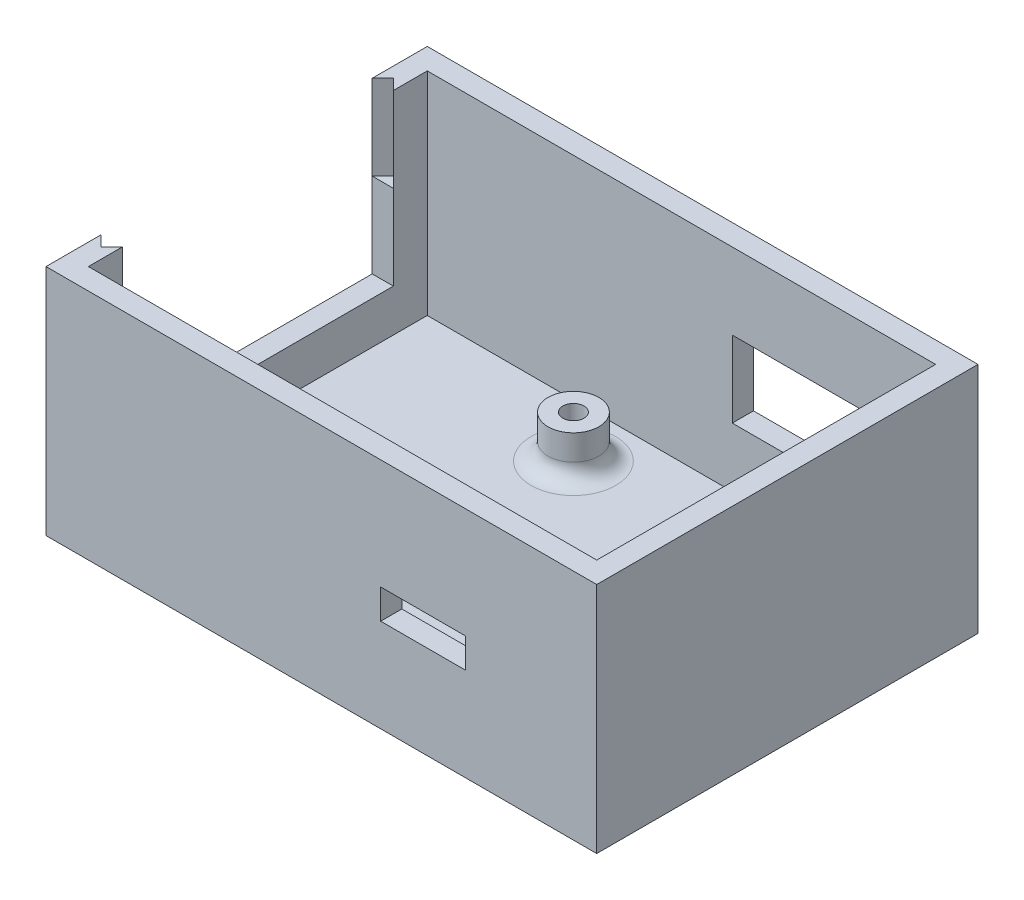
SolidWorks part; units mm, degrees
ref_plane "前视基准面" through (0, 0, 0) normal (0, 0, 1) x (1, 0, 0)
ref_plane "上视基准面" through (0, 0, 0) normal (0, 1, 0) x (1, 0, 0)
ref_plane "右视基准面" through (0, 0, 0) normal (1, 0, 0) x (0, 0, -1)
sketch "草图1" plane through (0, 0, 0) normal (0, 1, 0) x (1, 0, 0)
  line L1 (-32.5, 22.5) -> (32.5, 22.5)
  line L2 (-32.5, 22.5) -> (-32.5, -22.5)
  line L3 (-32.5, -22.5) -> (32.5, -22.5)
  line L4 (32.5, 22.5) -> (32.5, -22.5)
  line L5 (-32.5, 22.5) -> (32.5, -22.5) construction
  line L6 (-32.5, -22.5) -> (32.5, 22.5) construction
  point P0 (0, 0)
  dimension "D1" = 65
  dimension "D2" = 45
extrude "凸台-拉伸1" add sketch "草图1" along normal blind 27.5
shell "抽壳1" thickness 2.5 removed face at (0, 27.5, 0)
sketch "草图3" plane through (-30, 0, 0) normal (1, 0, 0) x (0, 0, -1)
  line L0 (20, 27.5) -> (-20, 27.5) construction
  line L1 (16, 27.5) -> (-16, 27.5)
  line L2 (16, 27.5) -> (16, 7.5)
  line L3 (16, 7.5) -> (-16, 7.5)
  line L4 (-16, 27.5) -> (-16, 7.5)
  line L5 (0, 27.5) -> (0, 7.5) construction
  line L6 (20, 2.5) -> (-20, 2.5) construction
  point P10 (0, 2.5)
  dimension "D1" = 32
  dimension "D2" = 5
extrude "切除-拉伸1" cut sketch "草图3" against normal through all
sketch "草图4" plane through (0, 27.5, 0) normal (0, 1, 0) x (1, 0, 0)
  line L0 (-32.5, 16) -> (-31.25, 17.25)
  line L1 (-31.25, 17.25) -> (-30, 16)
  line L2 (-32.5, 16) -> (-30, 16)
  line L3 (-32.5, -16) -> (-30, -16)
  line L4 (-30, 20) -> (-30, -20) construction
  line L5 (-32.5, -16) -> (-30, -16) construction
  line L6 (-30, -16) -> (-31.25, -17.25)
  line L7 (-31.25, -17.25) -> (-32.5, -16)
extrude "切除-拉伸2" cut sketch "草图4" against normal offset from surface (10 mm away) 10 up to face at (-31.25, 7.5, 0)
sketch "草图5" plane through (0, 2.5, 0) normal (0, 1, 0) x (1, 0, 0)
  line L0 (0, 0) -> (-37.9244, 0) construction
  line L1 (-32.5, -16) -> (-32.5, 16) construction
  circle A0 centre (-6.5, 13.75) radius 3
  circle A1 centre (-6.5, -13.75) radius 3
  circle A2 centre (-6.5, 13.75) radius 1.25
  circle A3 centre (-6.5, -13.75) radius 1.25
  dimension "D1" = 6
  dimension "D2" = 13.75
  dimension "D5" = 2.5
  dimension "D3" = 27.5
  dimension "D4" = 26
extrude "凸台-拉伸2" add sketch "草图5" along normal blind 5
sketch "草图6" plane through (0, 2.5, 0) normal (0, 1, 0) x (1, 0, 0)
  line L0 (30, -20) -> (30, 20) construction
  line L1 (30, 20) -> (-30, 20) construction
  circle A0 centre (20, -7) radius 3
  circle A1 centre (20, -7) radius 0.75
  dimension "D2" = 6
  dimension "D3" = 1.5
  dimension "D1" = 10
  dimension "D4" = 27
extrude "凸台-拉伸3" add sketch "草图6" along normal blind 5
sketch "草图7" plane through (0, 0, -20) normal (0, 0, 1) x (1, 0, 0)
  line L0 (30, 27.5) -> (30, 2.5) construction
  line L1 (28, 18.5) -> (6, 18.5)
  line L2 (28, 18.5) -> (28, 9.5)
  line L3 (28, 9.5) -> (6, 9.5)
  line L4 (6, 18.5) -> (6, 9.5)
  line L5 (30, 2.5) -> (-30, 2.5) construction
  dimension "D1" = 2
  dimension "D2" = 9
  dimension "D3" = 22
  dimension "D4" = 7
extrude "切除-拉伸3" cut sketch "草图7" against normal through all
sketch "草图8" plane through (0, 0, 20) normal (0, 0, -1) x (-1, 0, 0)
  line L0 (-30, 27.5) -> (-30, 2.5) construction
  line L1 (-7, 14.5) -> (-17, 14.5)
  line L2 (-7, 14.5) -> (-7, 11)
  line L3 (-7, 11) -> (-17, 11)
  line L4 (-17, 14.5) -> (-17, 11)
  line L5 (30, 2.5) -> (-30, 2.5) construction
  dimension "D1" = 13
  dimension "D2" = 10
  dimension "D3" = 3.5
  dimension "D4" = 8.5
extrude "切除-拉伸4" cut sketch "草图8" against normal through all
fillet "圆角1" radius 2 3 edges at (20, 2.5, 10) (-6.5, 2.5, 16.75) (-6.5, 2.5, -10.75)
